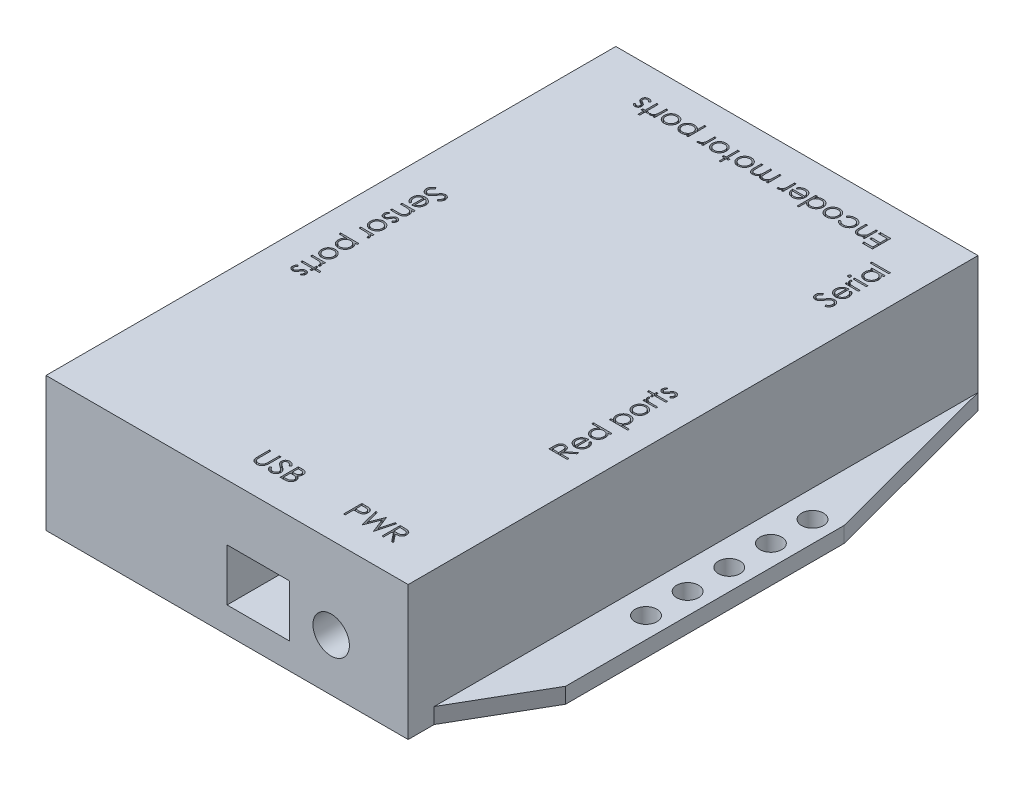
SolidWorks part; units mm, degrees
ref_plane "Front Plane" through (0, 0, 0) normal (0, 0, 1) x (1, 0, 0)
ref_plane "Top Plane" through (0, 0, 0) normal (0, 1, 0) x (1, 0, 0)
ref_plane "Right Plane" through (0, 0, 0) normal (1, 0, 0) x (0, 0, -1)
sketch "Sketch1" plane through (0, 0, 0) normal (0, 1, 0) x (1, 0, 0)
  line L1 (-34.8, 0) -> (34.8, 0)
  line L2 (-34.8, 0) -> (-34.8, 109.5)
  line L3 (-34.8, 109.5) -> (34.8, 109.5)
  line L4 (34.8, 0) -> (34.8, 109.5)
  point P6 (0, 0)
  dimension "D1" = 69.6
  dimension "D2" = 109.5
extrude "Boss-Extrude1" add sketch "Sketch1" along normal blind 25.8
sketch "Sketch2" plane through (0, 0, 0) normal (0, 1, 0) x (1, 0, 0)
  line L0 (-34.8, 109.5) -> (-44.05, 74.5)
  line L1 (-34.8, 109.5) -> (-34.8, 0) construction
  line L2 (-44.05, 74.5) -> (-44.05, 21)
  line L3 (-44.05, 21) -> (-34.8, 5)
  line L4 (-34.8, 5) -> (-34.8, 109.5)
  dimension "D3" = 16
  dimension "D1" = 35
  dimension "D4" = 5
  dimension "D2" = 44.05
extrude "Boss-Extrude2" add sketch "Sketch2" along normal blind 3
sketch "Sketch3" plane through (0, 3, 0) normal (0, 1, 0) x (1, 0, 0)
  line L0 (0, -1000) -> (0, 49000) construction
  line L1 (-40, 13.9946) -> (-40, 89.8243) construction
  line L2 (-34.8, 109.5) -> (-44.05, 74.5) construction
  line L3 (-44.05, 21) -> (-34.8, 5) construction
  line L4 (34.8, 109.5) -> (-34.8, 109.5) construction
  line L5 (-34.8, 0) -> (34.8, 0) construction
  circle A5 centre (-40, 72.5) radius 2.1
  circle A6 centre (-40, 64.5) radius 2.1
  circle A7 centre (-40, 56.5) radius 2.1
  circle A8 centre (-40, 48.5) radius 2.1
  circle A9 centre (-40, 40.5) radius 2.1
  dimension "D1" = 4.2
  dimension "D2" = 16
  dimension "D3" = 16
  dimension "D4" = 8
  dimension "D5" = 8
  dimension "D8" = 40
  dimension "D6" = 39.1
  dimension "D7" = 42.6
extrude "Cut-Extrude1" cut sketch "Sketch3" against normal through all
mirror "Mirror1" about plane through (0, 0, 0) normal (1, 0, 0) of "Cut-Extrude1", "Boss-Extrude2"
sketch "Sketch4" plane through (0, 0, 0) normal (0, 0, 1) x (1, 0, 0)
  line L0 (-34.8, 0) -> (34.8, 0) construction
  line L1 (0, 15) -> (12, 15)
  line L2 (0, 15) -> (0, 5)
  line L3 (0, 5) -> (12, 5)
  line L4 (12, 15) -> (12, 5)
  circle A0 centre (20, 10) radius 3.5
  point P14 (12, 10)
  dimension "D3" = 7
  dimension "D5" = 8
  dimension "D1" = 12
  dimension "D2" = 10
  dimension "D4" = 5
extrude "Cut-Extrude2" cut sketch "Sketch4" against normal blind 10
sketch "Sketch5" plane through (0, 25.8, 0) normal (0, 1, 0) x (1, 0, 0)
  line L0 (-34.8, 103.95) -> (34.8, 103.95) construction
  line L1 (-34.8, 109.5) -> (-34.8, 0) construction
  line L2 (34.8, 0) -> (34.8, 109.5) construction
  line L3 (34.8, 109.5) -> (-34.8, 109.5) construction
  line L4 (-34.8, 5.55) -> (34.8, 5.55) construction
  line L5 (-34.8, 0) -> (34.8, 0) construction
  line L6 (-29.25, 5.55) -> (-29.25, 103.95) construction
  line L7 (29.25, 103.95) -> (29.25, 5.55) construction
  text T0 "Encoder motor ports"
  text T1 "USB       PWR      "
  text T2 "Sensor ports"
  text T3 "Red ports                     Serial    "
  dimension "D1" = 5.55
  dimension "D2" = 5.55
  dimension "D3" = 5.55
  dimension "D4" = 5.55
extrude "Cut-Extrude3" cut sketch "Sketch5" against normal blind 1
equation "\"width\"= 24"
equation "\"thk\"= 3"
equation "\"holesize\"= 4.2"
equation "\"holedistance\"= ( 20 + 12 ) / 2"
equation "\"threaded_hole\"= 3.9"
equation "\"fillet_radius\"= 2"
equation "\"ground_clearance\"= 25"
equation "\"tire_thk\"= 4"
equation "\"innerwheel_diam\" = \"wheel_diam\"-2*\"tire_thk\""
equation "\"innerwheel_thk\"= 8"
equation "\"wheel_diam\"= 2*(\"width\"/2+\"ground_clearance\")"
equation "\"D1@Sketch3\"=\"holesize\""
equation "\"D2@Sketch3\"=\"holedistance\""
equation "\"D3@Sketch3\"=\"holedistance\""
equation "\"D4@Sketch3\"=\"D2@Sketch3\"/2"
equation "\"D5@Sketch3\"=\"D3@Sketch3\"/2"
equation "\"D2@Sketch5\"=\"D1@Sketch5\""
equation "\"D3@Sketch5\"=\"D1@Sketch5\""
equation "\"D4@Sketch5\"=\"D2@Sketch5\""
equation "\"D8@Sketch3\"=80/2"
equation "\"D2@Sketch2\"=88.1/2"
